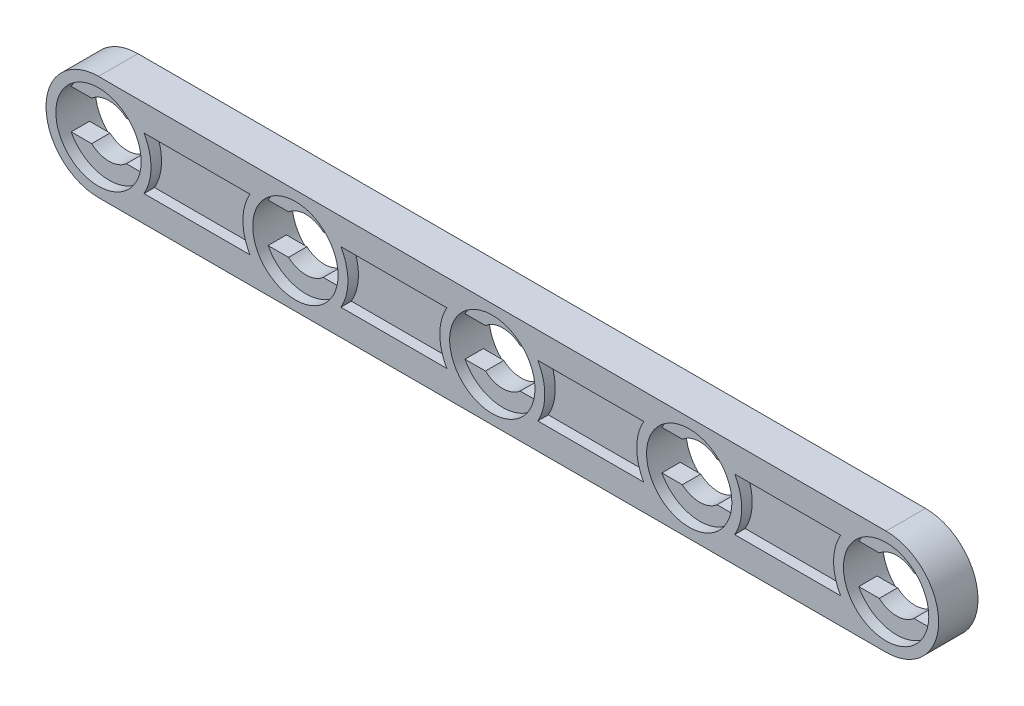
SolidWorks part; units mm, degrees
ref_plane "前视基准面" through (0, 0, 0) normal (0, 0, 1) x (1, 0, 0)
ref_plane "上视基准面" through (0, 0, 0) normal (0, 1, 0) x (1, 0, 0)
ref_plane "右视基准面" through (0, 0, 0) normal (1, 0, 0) x (0, 0, -1)
sketch "草图1" plane through (0, 0, 0) normal (0, 0, 1) x (1, 0, 0)
  line L1 (0, 4) -> (60, 4)
  line L3 (0, -4) -> (60, -4)
  arc A0 (0, 4) -> (0, -4) centre (0, 0) ccw
  arc A2 (60, -4) -> (60, 4) centre (60, 0) ccw
extrude "凸台-拉伸1" add sketch "草图1" against normal blind 3
sketch "草图2" plane through (0, 0, 0) normal (0, 0, 1) x (1, 0, 0)
  line L0 (1.3229, -1.5) -> (2.8831, -1.5)
  line L1 (-2.8831, -1.5) -> (-1.3229, -1.5)
  line L2 (1.3229, 1.5) -> (2.8831, 1.5)
  line L3 (-2.8831, 1.5) -> (-1.3229, 1.5)
  arc A0 (1.3229, 1.5) -> (-1.3229, 1.5) centre (0, 0) ccw
  arc A1 (-2.8831, 1.5) -> (-2.8831, -1.5) centre (0, 0) ccw
  arc A3 (2.8831, -1.5) -> (2.8831, 1.5) centre (0, 0) ccw
  arc A4 (-1.3229, -1.5) -> (1.3229, -1.5) centre (0, 0) ccw
extrude "切除-拉伸1" cut sketch "草图2" against normal up to next
sketch "草图3" plane through (0, 0, 0) normal (0, 0, 1) x (1, 0, 0)
  circle A1 centre (0, 0) radius 3.25
extrude "切除-拉伸2" cut sketch "草图3" against normal blind 0.8
extrude "切除-拉伸3" cut sketch "草图3<2>" along normal blind 0.8 from offset 3 offset against normal yes
sketch "草图3<2>" plane through (0, 0, 0) normal (0, 0, 1) x (1, 0, 0) same geometry as "草图3"
sketch "草图4" plane through (0, 0, 0) normal (0, 0, 1) x (1, 0, 0)
  line L1 (3.4641, 2) -> (11.5359, 2)
  line L3 (3.4641, -2) -> (11.5359, -2)
  arc A0 (11.5359, 2) -> (11.5359, -2) centre (15, 0) ccw
  arc A2 (3.4641, -2) -> (3.4641, 2) centre (0, 0) ccw
extrude "切除-拉伸4" cut sketch "草图4" against normal blind 0.8
sketch "草图5" plane through (0, 0, -3) normal (0, 0, -1) x (-1, 0, 0)
  line L1 (-4, -2) -> (-11, -2)
  line L2 (-4, -2) -> (-4, 2)
  line L3 (-4, 2) -> (-11, 2)
  line L4 (-11, -2) -> (-11, 2)
extrude "切除-拉伸6" cut sketch "草图5" against normal blind 0.8
ref_plane "基准面1" through (7.5, 0, 0) normal (1, 0, 0) x (0, 0, -1)
mirror "镜向1" about plane through (7.5, 0, 0) normal (1, 0, 0) of "切除-拉伸3", "切除-拉伸2", "切除-拉伸1"
ref_plane "基准面2" through (22.5, 0, 0) normal (1, 0, 0) x (0, 0, -1)
mirror "镜向2" about plane through (22.5, 0, 0) normal (1, 0, 0) of "镜向1", "切除-拉伸3", "切除-拉伸2", "切除-拉伸1"
ref_plane "基准面3" through (15, 0, 0) normal (1, 0, 0) x (0, 0, -1)
mirror "镜向3" about plane through (15, 0, 0) normal (1, 0, 0) of "切除-拉伸6", "切除-拉伸4"
mirror "镜向4" about plane through (22.5, 0, 0) normal (1, 0, 0) of "切除-拉伸4", "切除-拉伸6"
ref_plane "基准面4" through (30, 0, 0) normal (1, 0, 0) x (0, 0, -1)
mirror "镜向5" about plane through (30, 0, 0) normal (1, 0, 0) of "切除-拉伸3", "切除-拉伸2", "切除-拉伸1"
ref_plane "基准面5" through (30, 0, 0) normal (1, 0, 0) x (0, 0, -1)
mirror "镜向6" about plane through (30, 0, 0) normal (1, 0, 0) of "切除-拉伸6", "切除-拉伸4"
